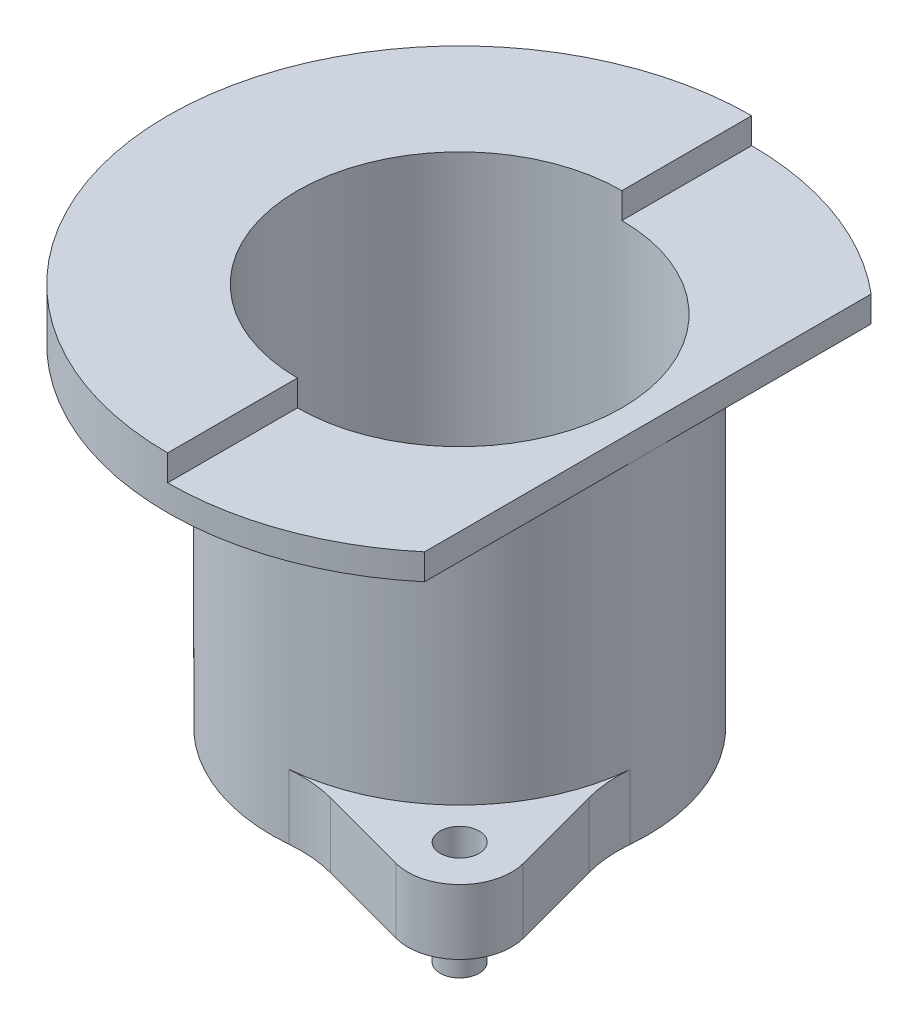
SolidWorks part; units mm, degrees
ref_plane "前基準面" through (0, 0, 0) normal (0, 0, 1) x (1, 0, 0)
ref_plane "上基準面" through (0, 0, 0) normal (0, 1, 0) x (1, 0, 0)
ref_plane "右基準面" through (0, 0, 0) normal (1, 0, 0) x (0, 0, -1)
sketch "草圖2" plane through (0, 0, 0) normal (0, 1, 0) x (1, 0, 0)
  circle A0 centre (0, 0) radius 12.5
  circle A1 centre (0, 0) radius 14.5
  dimension "D1" = 25
  dimension "D2" = 29
extrude "填料-伸長1" add sketch "草圖2" along normal blind 25.5
surface "曲面-偏移1" parameters "D1"=0
sketch "草圖3" plane through (0, 25.5, 0) normal (0, 1, 0) x (1, 0, 0)
  circle A0 centre (0, 0) radius 12.5
  circle A1 centre (0, 0) radius 22.5
  dimension "D1" = 25
  dimension "D2" = 45
extrude "填料-伸長2" add sketch "草圖3" along normal blind 2
sketch "草圖4" plane through (0, 27.5, 0) normal (0, 1, 0) x (1, 0, 0)
  line L0 (0, 22.5) -> (0, 12.5)
  line L1 (0, -12.5) -> (0, -22.5)
  arc A0 (0, 22.5) -> (0, -22.5) centre (0, 0) ccw
  arc A1 (0, 12.5) -> (0, -12.5) centre (0, 0) ccw
  circle A2 centre (0, 0) radius 22.5 construction
  circle A3 centre (0, 0) radius 12.5 construction
extrude "填料-伸長3" add sketch "草圖4" along normal blind 2
sketch "草圖6" plane through (0, 25.5, 0) normal (0, -1, 0) x (1, 0, 0)
  line L1 (14.5, 29.3958) -> (53.339, 29.3958)
  line L2 (14.5, 29.3958) -> (14.5, -31.2101)
  line L3 (14.5, -31.2101) -> (53.339, -31.2101)
  line L4 (53.339, 29.3958) -> (53.339, -31.2101)
  circle A0 centre (0, 0) radius 14.5 construction
extrude "除料-伸長1" cut sketch "草圖6" against normal blind 10
surface "曲面-偏移2" parameters "D1"=0
sketch "草圖7" plane through (0, 0, 0) normal (0, -1, 0) x (1, 0, 0)
  line L0 (-12.7279, -12.7279) -> (12.7279, 12.7279) construction
  line L1 (-11.6926, -16.5916) -> (-2.8391, -14.2193)
  line L2 (0, 0) -> (5.9332, -5.9332) construction
  line L3 (-16.5916, -11.6926) -> (-14.2193, -2.8391)
  line L4 (16.5916, 11.6926) -> (14.2193, 2.8391)
  line L5 (11.6926, 16.5916) -> (2.8391, 14.2193)
  circle A0 centre (12.7279, 12.7279) radius 1.5 construction
  circle A1 centre (-12.7279, -12.7279) radius 1.5 construction
  circle A2 centre (12.7279, 12.7279) radius 1.5
  circle A3 centre (-12.7279, -12.7279) radius 1.5
  arc A4 (-16.5916, -11.6926) -> (-11.6926, -16.5916) centre (-12.7279, -12.7279) ccw
  circle A5 centre (0, 0) radius 14.5 construction
  circle A6 centre (0, 0) radius 14.5 construction
  arc A7 (11.6926, 16.5916) -> (16.5916, 11.6926) centre (12.7279, 12.7279) cw
  circle A8 centre (0, 0) radius 14.5
  point P8 (-15.5563, -15.5563)
  circle M6 centre (0, 0) radius 14.5
  circle M7 centre (0, 0) radius 12.5
  dimension "D1" = 4
  dimension "D2" = 120
extrude "填料-伸長4" add sketch "草圖7" against normal blind 5 contours L3 A4 L1 A3 M6 | M6 M7 | A7 L5 L4 A2 M6 region at (-15.4175, 0, -15.4175) region at (-9.963, 0, -9.963) region at (7.3167, 0, 15.2158)
fillet "圓角1" radius 10 4 edges at (-14.2193, 2.5, -2.8391) (-2.8391, 2.5, -14.2193) (14.2193, 2.5, 2.8391) (2.8391, 2.5, 14.2193)
